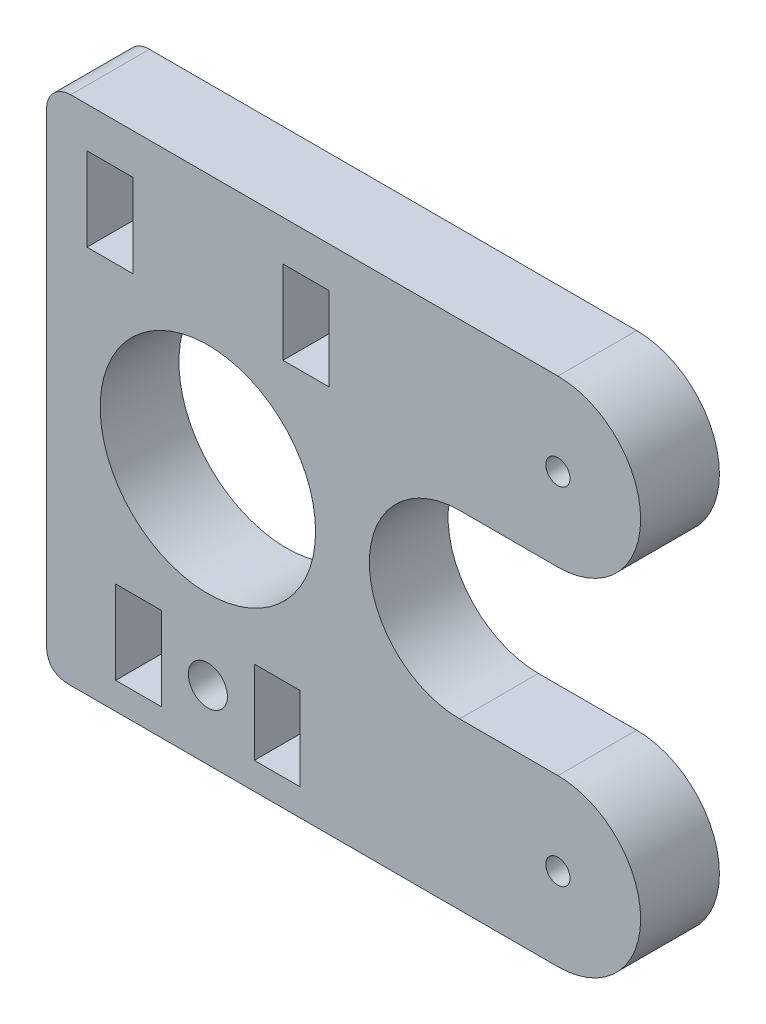
SolidWorks part; units mm, degrees
material "Acrylic (Medium-high impact)"
ref_plane "Front Plane" through (0, 0, 0) normal (0, 0, 1) x (1, 0, 0)
ref_plane "Top Plane" through (0, 0, 0) normal (0, 1, 0) x (1, 0, 0)
ref_plane "Right Plane" through (0, 0, 0) normal (1, 0, 0) x (0, 0, -1)
sketch "Sketch1" plane through (0, 0, 0) normal (0, 0, 1) x (1, 0, 0)
  line L0 (669.2168, 349.7655) -> (648.5357, 349.7655)
  line L1 (646.7465, 347.9762) -> (646.7465, 313.4546)
  line L2 (648.7733, 311.7655) -> (669.2168, 311.7655)
  line L3 (653.1465, 340.5655) -> (653.1465, 346.7655)
  line L4 (653.1465, 346.7655) -> (649.7465, 346.7655)
  line L5 (649.7465, 346.7655) -> (649.7465, 340.5655)
  line L6 (649.7465, 340.5655) -> (653.1465, 340.5655)
  line L7 (651.8765, 313.7655) -> (655.2765, 313.7655)
  line L8 (655.2765, 313.7655) -> (655.2765, 319.9655)
  line L9 (655.2765, 319.9655) -> (651.8765, 319.9655)
  line L10 (651.8765, 319.9655) -> (651.8765, 313.7655)
  line L11 (667.7065, 340.5655) -> (667.7065, 346.7655)
  line L12 (667.7065, 346.7655) -> (664.3065, 346.7655)
  line L13 (664.3065, 346.7655) -> (664.3065, 340.5655)
  line L14 (664.3065, 340.5655) -> (667.7065, 340.5655)
  line L15 (662.1765, 319.9655) -> (662.1765, 313.7655)
  line L16 (662.1765, 313.7655) -> (665.5765, 313.7655)
  line L17 (665.5765, 313.7655) -> (665.5765, 319.9655)
  line L18 (665.5765, 319.9655) -> (662.1765, 319.9655)
  line L19 (-318.4867, 330.7655) -> (49681.5133, 330.7655) construction
  line L20 (669.2168, -652.8598) -> (669.2168, 49347.1402) construction
  line L21 (653.1465, 340.5655) -> (664.3065, 340.5655) construction
  line L22 (657.2765, 316.8655) -> (655.2765, 316.8655) construction
  line L23 (660.1765, 316.8655) -> (662.1765, 316.8655) construction
  line L24 (658.7265, -666.0306) -> (658.7265, 49333.9694) construction
  line L25 (669.2168, 311.7655) -> (684.7265, 311.7655)
  line L26 (669.2168, 349.7655) -> (684.7265, 349.7655)
  line L27 (684.7265, 317.9129) -> (684.7265, 330.7655) construction
  line L28 (684.7265, 330.7655) -> (684.7265, 343.618) construction
  line L29 (684.7265, -670.5722) -> (684.7265, 49329.4278) construction
  line L30 (662.1765, 330.7655) -> (662.1765, 349.7655) construction
  line L31 (662.1765, 330.7655) -> (662.1765, 311.7655) construction
  line L32 (684.7265, 337.4705) -> (677.4255, 337.4705)
  line L33 (684.7265, 324.0604) -> (677.4255, 324.0604)
  circle A0 centre (684.7265, 343.618) radius 0.8999
  circle A1 centre (684.7265, 317.9129) radius 0.8999
  arc A2 (684.7265, 311.7655) -> (684.7265, 324.0604) centre (684.7265, 317.9129) ccw
  circle A3 centre (658.7265, 316.8655) radius 1.45
  arc A4 (646.7465, 347.9762) -> (648.5357, 349.7655) centre (648.5357, 347.9762) cw
  arc A5 (684.7265, 349.7655) -> (684.7265, 337.4705) centre (684.7265, 343.618) cw
  arc A6 (677.4255, 337.4705) -> (677.4255, 324.0604) centre (677.4255, 330.7655) ccw
  circle A8 centre (658.7265, 330.7655) radius 8
  spline S7 degree 2 poles (646.7465, 313.4546) (646.7465, 311.6465) (648.7733, 311.7655) knots 0 0 0 1 1 1
  point P27 (658.7265, 340.5655)
  dimension "D5" = 2.9
  dimension "D12" = 26
  dimension "D1" = 2
  dimension "D2" = 6.2
  dimension "D3" = 3.4
  dimension "D4" = 3.4
  dimension "D6" = 11.16
  dimension "D7" = 3
  dimension "D8" = 3
  dimension "D9" = 2
  dimension "D10" = 33
  dimension "D11" = 12.8525
extrude "Boss-Extrude2" add sketch "Sketch1" along normal blind 5.85
